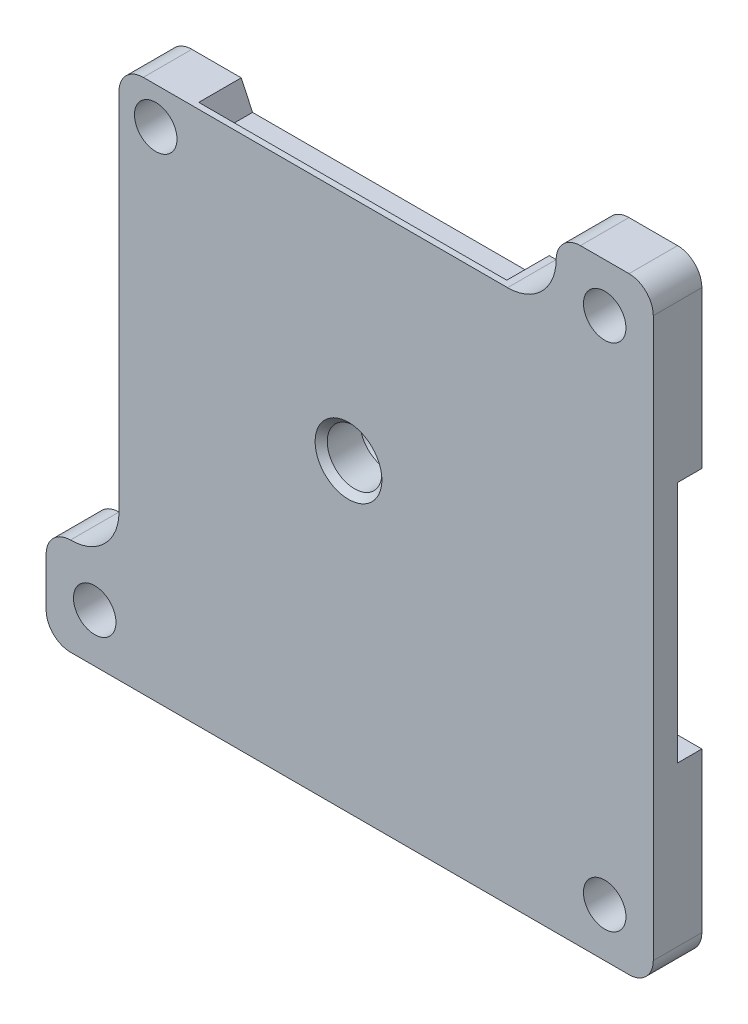
SolidWorks part; units mm, degrees
note: '?' marks a value the reader was unsure of.
ref_plane "Front Plane" through (0, 0, 0) normal (0, 0, 1) x (1, 0, 0)
ref_plane "Top Plane" through (0, 0, 0) normal (0, 1, 0) x (1, 0, 0)
ref_plane "Right Plane" through (0, 0, 0) normal (1, 0, 0) x (0, 0, -1)
sketch "Sketch1" plane through (0, 0, 0) normal (0, 0, 1) x (1, 0, 0)
  line L0 (39, -39) -> (-3, -39) construction
  line L1 (39, -39) -> (39, 3) construction
  line L2 (43, -43) -> (43, 7)
  line L3 (43, 7) -> (35, 7)
  line L4 (35, 7) -> (35, 1)
  line L5 (41, 7) -> (37, 7) construction
  line L6 (43, 3) -> (43, 5) construction
  line L7 (39, -39) -> (10.1301, -10.1301) construction
  line L8 (35, 1) -> (-1, 1)
  line L9 (25.4326, 1) -> (35, 1) construction
  line L10 (35, 5) -> (35, 1) construction
  line L11 (43, -43) -> (-7, -43)
  line L12 (-7, -43) -> (-7, -35)
  line L13 (-7, -35) -> (-1, -35)
  line L14 (-1, -35) -> (-1, 1)
  dimension "D1" = 45
extrude "Boss-Extrude1" add sketch "Sketch1" along normal blind 4
fillet "Fillet1" radius 2 6 edges at (-1, 1, 2) (35, 7, 2) (43, 7, 2) (43, -43, 2) (-7, -43, 2) (-7, -35, 2)
fillet "Fillet2" radius 4 2 edges at (35, 1, 2) (-1, -35, 2)
sketch "Sketch2" plane through (0, 0, 0) normal (0, 0, -1) x (-1, 0, 0)
  line L0 (-13.493, -13.493) -> (-21.7069, -21.7069) construction
  line L1 (-130, -17.75) -> (0, -13) construction
  line L2 (0, -22.5) -> (-130, -17.75) construction
  line L3 (-17.75, -130) -> (-22.5, 0) construction
  line L4 (-17.75, -130) -> (-13, 0) construction
  line L5 (-13.8037, -21.9956) -> (-21.9956, -13.8037) construction
  point P12 (-17.8997, -17.8997)
ref_axis "Axis1" through (17.8997, -17.8997, 0) along (0, 0, -1)?
ref_plane "Plane1" through (0, -17.8997, 0) normal (0, -1, 0) x (0, 0, -1)
sketch "Sketch3" plane through (0, 0, 0) normal (0, 0, -1) x (-1, 0, 0)
  circle A0 centre (-17.8997, -17.8997) radius 6
  dimension "D1" = 12
extrude "Cut-Extrude3" cut sketch "Sketch3" against normal through all
sketch "Sketch4" plane through (0, 0, 0) normal (0, 0, -1) x (-1, 0, 0)
  circle A0 centre (-39, 3) radius 1.75
  circle A1 centre (-39, -39) radius 1.75
  circle A2 centre (3, -39) radius 1.75
  circle A3 centre (-2.0253, -2.0253) radius 1.75
  dimension "D1" = 3.5
extrude "Cut-Extrude6" cut sketch "Sketch4" against normal through all
ref_plane "Plane2" through (17.8997, 0, 0) normal (-1, 0, 0) x (0, 0, 1)
sketch "Sketch5" plane through (17.8997, 0, 0) normal (-1, 0, 0) x (0, 0, 1)
  line L0 (2, -43) -> (0, -43)
  line L1 (0, -43) -> (0, -41)
  line L2 (0, -41) -> (2, -43)
  dimension "D1" = 2
extrude "Cut-Extrude7" cut sketch "Sketch5" against normal mid plane 20
ref_plane "Plane3" through (0, 0, 0) normal (-0.7071, -0.7071, 0) x (0.7071, -0.7071, 0)
sketch "Sketch6" plane through (17.8997, 0, 0) normal (-1, 0, 0) x (0, 0, 1)
  line L0 (0, 1) -> (0, -1)
  line L1 (0, -1) -> (1.5, -1)
  line L2 (1.5, -1) -> (3.5, 1)
  line L3 (3.5, 1) -> (0, 1)
  dimension "D1" = 135
  dimension "D2" = 1.5
  dimension "D3" = 2
extrude "Cut-Extrude8" cut sketch "Sketch6" against normal blind 12.533 and the other way blind 12.8323
chamfer "Chamfer1" distance 2 angle 25 2 edges at (5.0674, -1, 0.75) (30.4327, -1, 0.75)
mirror "Mirror1" about plane through (0, 0, 0) normal (-0.7071, -0.7071, 0) of "Chamfer1", "Cut-Extrude7", "Cut-Extrude8"
sketch "Sketch7" plane through (0, -17.8997, 0) normal (0, -1, 0) x (0, 0, -1)
  line L0 (0, 23.8997) -> (5, 21.0129)
  line L1 (5, 21.0129) -> (5, 18.8997)
  line L2 (5, 18.8997) -> (1.3651, 18.8997)
  line L3 (1.3651, 18.8997) -> (-0.8, 20.1497)
  line L4 (-0.8, 20.1497) -> (-4, 20.1497)
  line L5 (-4, 20.1497) -> (-4, 23.8997)
  line L6 (-4, 23.8997) -> (0, 23.8997)
  line L7 (-4, 23.8997) -> (-4, 11.8997) construction
  line L8 (0, 17.8997) -> (13.0291, 17.8997) construction
  line L9 (0, 27.8997) -> (0, 7.8997) construction
  line L10 (-4, -5) -> (-4, 41) construction
  dimension "D1" = 5
  dimension "D2" = 2
  dimension "D3" = 60
  dimension "D4" = 4.5
  dimension "D5" = 3.2
revolve "Revolve1" add sketch "Sketch7" angle 360 about L8
chamfer "Chamfer2" distance 0.5 angle 45 1 edges at (20.1497, -17.8997, 4)
